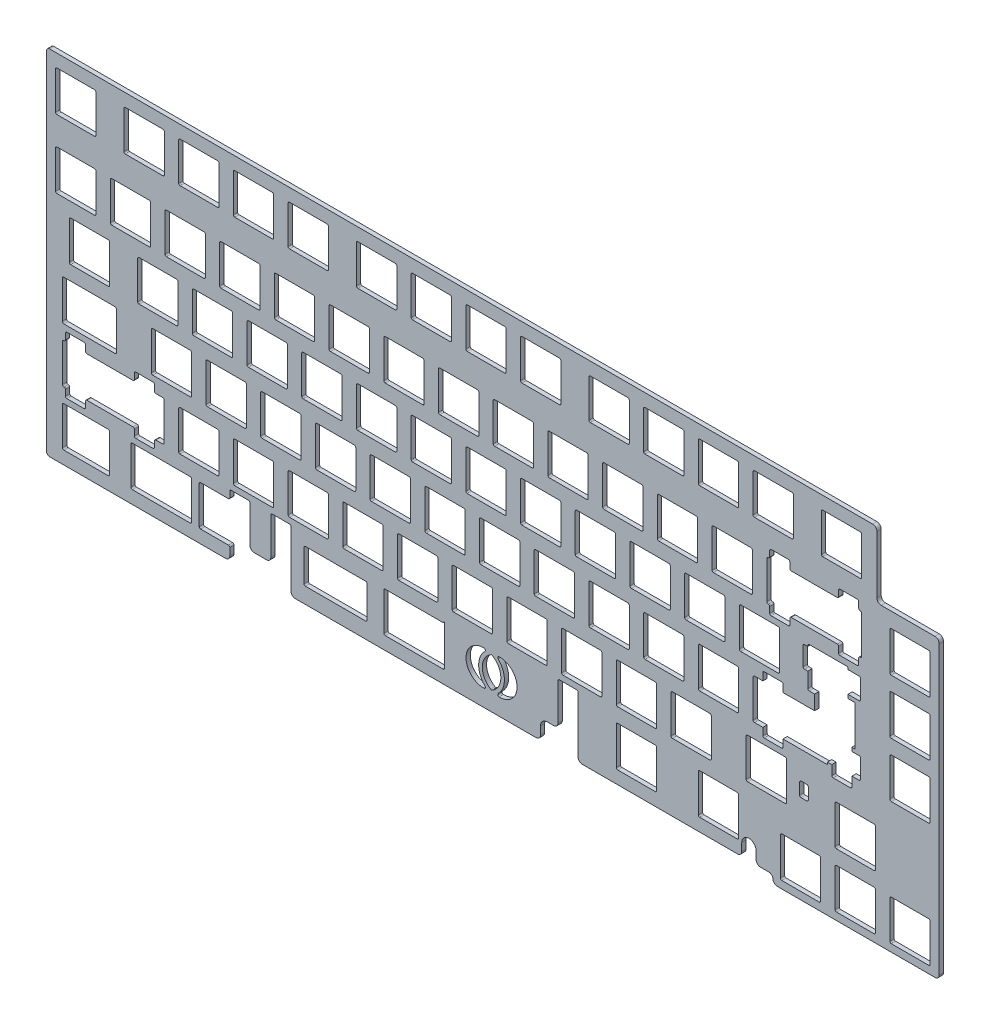
SolidWorks part; units mm, degrees
material "POM Acetal Copolymer"
ref_plane "Front Plane" through (0, 0, 0) normal (0, 0, 1) x (1, 0, 0)
ref_plane "Top Plane" through (0, 0, 0) normal (0, 1, 0) x (1, 0, 0)
ref_plane "Right Plane" through (0, 0, 0) normal (1, 0, 0) x (0, 0, -1)
sketch "Model" plane through (0, 0, 0) normal (0, 0, 1) x (1, 0, 0)
  line L0 (274.4928, 83.607) -> (287.4928, 83.607)
  line L1 (273.9928, 70.107) -> (273.9928, 75.3421)
  line L2 (8.8553, 129.8695) -> (8.8553, 63.082)
  line L3 (67.4518, 130.9695) -> (9.9553, 130.9695)
  line L4 (319.7678, 63.082) -> (319.7678, 106.4532)
  line L5 (195.4959, 7.957) -> (249.4928, 7.957)
  line L6 (86.9959, 28.958) -> (86.9959, 16.157)
  line L7 (187.4959, 29.458) -> (193.4959, 29.458)
  line L8 (193.9959, 28.958) -> (193.9959, 9.457)
  line L9 (186.9959, 16.157) -> (186.9959, 28.958)
  line L10 (87.4959, 29.458) -> (93.4959, 29.458)
  line L11 (126.357, 12.957) -> (126.357, 25.957)
  line L12 (62.0594, 12.957) -> (62.0594, 25.957)
  line L13 (38.2454, 12.957) -> (38.2454, 25.957)
  line L14 (14.4343, 12.957) -> (14.4343, 25.957)
  line L15 (72.207, 12.457) -> (62.5594, 12.457)
  line L16 (62.5594, 26.457) -> (72.207, 26.457)
  line L17 (59.3945, 25.957) -> (59.3945, 12.957)
  line L18 (58.8945, 12.457) -> (38.7454, 12.457)
  line L19 (38.7454, 26.457) -> (58.8945, 26.457)
  line L20 (30.8195, 25.957) -> (30.8195, 12.957)
  line L21 (30.3195, 12.457) -> (14.9343, 12.457)
  line L22 (14.9343, 26.457) -> (30.3195, 26.457)
  line L23 (93.9959, 28.958) -> (93.9959, 9.457)
  line L24 (146.9959, 12.457) -> (126.857, 12.457)
  line L25 (126.857, 26.457) -> (146.9959, 26.457)
  line L26 (147.4959, 26.7823) -> (147.4959, 12.957)
  line L27 (9.9553, 7.957) -> (71.207, 7.957)
  line L28 (95.4959, 7.957) -> (179.3625, 7.957)
  line L29 (263.3678, 5.0945) -> (318.2678, 5.0945)
  line L30 (180.8625, 12.157) -> (180.8625, 9.457)
  line L31 (250.9928, 12.157) -> (250.9928, 9.457)
  line L32 (255.9928, 12.157) -> (255.9928, 9.457)
  line L33 (183.3625, 14.657) -> (185.4959, 14.657)
  line L34 (81.207, 14.657) -> (85.4959, 14.657)
  line L35 (257.4928, 7.957) -> (260.371, 7.957)
  line L36 (8.8553, 63.082) -> (8.8553, 9.057)
  line L37 (319.7678, 63.082) -> (319.7678, 6.5945)
  line L38 (75.4518, 130.9695) -> (248.4268, 130.9695)
  line L39 (256.4268, 130.9695) -> (296.5553, 130.9695)
  line L40 (298.0553, 129.4695) -> (298.0553, 109.4532)
  line L41 (299.5553, 107.9532) -> (318.2678, 107.9532)
  line L42 (271.6572, 41.007) -> (273.6572, 41.007)
  line L43 (274.1572, 40.507) -> (274.1572, 36.507)
  line L44 (273.6572, 36.007) -> (271.6572, 36.007)
  line L45 (271.1572, 36.507) -> (271.1572, 40.507)
  line L46 (260.7295, 105.157) -> (260.7295, 103.157)
  line L47 (268.2295, 102.657) -> (284.2295, 102.657)
  line L48 (268.2295, 88.657) -> (284.2295, 88.657)
  line L49 (261.2295, 105.657) -> (267.2295, 105.657)
  line L50 (261.2295, 85.657) -> (267.2295, 85.657)
  line L51 (267.7295, 103.157) -> (267.7295, 105.157)
  line L52 (267.7295, 88.157) -> (267.7295, 86.157)
  line L53 (291.7295, 105.157) -> (291.7295, 103.157)
  line L54 (291.2295, 105.657) -> (285.2295, 105.657)
  line L55 (291.2295, 85.657) -> (285.2295, 85.657)
  line L56 (284.7295, 103.157) -> (284.7295, 105.157)
  line L57 (284.7295, 88.157) -> (284.7295, 86.157)
  line L58 (258.3508, 50.557) -> (258.3508, 48.057)
  line L59 (265.3508, 50.557) -> (280.8516, 50.557)
  line L60 (258.8508, 67.557) -> (264.8508, 67.557)
  line L61 (258.8508, 47.557) -> (264.8508, 47.557)
  line L62 (265.3508, 64.557) -> (265.3508, 67.057)
  line L63 (265.3508, 50.557) -> (265.3508, 48.057)
  line L64 (288.8508, 47.557) -> (282.8508, 47.557)
  line L65 (282.3508, 51.3421) -> (282.3508, 48.057)
  line L66 (15.4632, 48.0073) -> (15.4632, 46.007)
  line L67 (22.9632, 45.5073) -> (38.9632, 45.5073)
  line L68 (22.9632, 31.5073) -> (38.9632, 31.5073)
  line L69 (15.9632, 48.5073) -> (21.9632, 48.5073)
  line L70 (15.9632, 28.5073) -> (21.9632, 28.5073)
  line L71 (22.4632, 46.0073) -> (22.4632, 48.0073)
  line L72 (22.4632, 31.0073) -> (22.4632, 29.0073)
  line L73 (46.4632, 48.0073) -> (46.4632, 46.007)
  line L74 (45.9632, 48.5073) -> (39.9632, 48.5073)
  line L75 (45.9632, 28.5073) -> (39.9632, 28.5073)
  line L76 (39.4632, 46.0073) -> (39.4632, 48.0073)
  line L77 (39.4632, 31.0073) -> (39.4632, 29.0073)
  line L78 (258.3508, 50.557) -> (255.4453, 50.557)
  line L79 (276.3765, 69.607) -> (274.4928, 69.607)
  line L80 (276.3765, 64.557) -> (276.3765, 69.607)
  line L81 (292.3508, 82.2801) -> (292.3508, 75.8421)
  line L82 (292.3508, 58.2801) -> (292.3508, 51.8421)
  line L83 (291.8508, 82.7801) -> (287.9953, 82.7801)
  line L84 (255.4453, 64.557) -> (258.3508, 64.557)
  line L85 (290.3765, 74.0611) -> (290.3765, 60.0611)
  line L86 (254.9453, 64.057) -> (254.9453, 51.057)
  line L87 (287.9953, 75.3421) -> (291.8508, 75.3421)
  line L88 (289.3508, 58.7801) -> (291.8508, 58.7801)
  line L89 (290.3765, 74.0611) -> (287.9953, 74.0611)
  line L90 (287.9953, 74.0611) -> (287.9953, 75.3421)
  line L91 (289.3508, 58.7801) -> (289.3508, 60.0611)
  line L92 (289.3508, 60.0611) -> (290.3765, 60.0611)
  line L93 (282.3508, 51.3421) -> (280.8516, 51.3421)
  line L94 (280.8516, 51.3421) -> (280.8516, 50.557)
  line L95 (258.3508, 67.057) -> (258.3508, 64.557)
  line L96 (289.3508, 48.057) -> (289.3508, 51.3421)
  line L97 (291.8508, 51.3421) -> (289.3508, 51.3421)
  line L98 (287.9928, 83.107) -> (287.9953, 82.7801)
  line L99 (265.3508, 64.557) -> (276.3765, 64.557)
  line L100 (272.3508, 82.2801) -> (272.3508, 75.8421)
  line L101 (272.8508, 82.7801) -> (273.9928, 82.7801)
  line L102 (273.9928, 75.3421) -> (272.8508, 75.3421)
  line L103 (273.9928, 82.7801) -> (273.9928, 83.107)
  line L104 (259.7053, 89.157) -> (259.7053, 102.157)
  line L105 (292.7553, 102.157) -> (292.7553, 89.157)
  line L106 (291.7295, 86.157) -> (291.7295, 88.157)
  line L107 (292.2295, 88.657) -> (292.2553, 88.657)
  line L108 (292.2295, 102.657) -> (292.2553, 102.657)
  line L109 (260.2053, 102.657) -> (260.2295, 102.657)
  line L110 (260.7295, 86.157) -> (260.7295, 88.157)
  line L111 (260.2295, 88.657) -> (260.2053, 88.657)
  line L112 (49.8678, 45.007) -> (49.8678, 32.007)
  line L113 (46.4632, 29.0073) -> (46.4632, 31.007)
  line L114 (46.9632, 31.507) -> (49.3678, 31.507)
  line L115 (46.9632, 45.507) -> (49.3678, 45.507)
  line L116 (14.4365, 32.007) -> (14.4365, 45.007)
  line L117 (15.4632, 29.0073) -> (15.4632, 31.007)
  line L118 (14.9632, 31.507) -> (14.9365, 31.507)
  line L119 (14.9365, 45.507) -> (14.9632, 45.507)
  line L120 (79.707, 28.958) -> (79.707, 16.157)
  line L121 (72.707, 11.957) -> (72.707, 9.457)
  line L122 (72.707, 26.957) -> (72.707, 28.958)
  line L123 (73.207, 29.458) -> (79.207, 29.458)
  line L124 (120.5413, 13.957) -> (120.5413, 24.957)
  line L125 (99.0413, 13.457) -> (120.0413, 13.457)
  line L126 (98.5413, 24.957) -> (98.5413, 13.957)
  line L127 (120.0413, 25.457) -> (99.0413, 25.457)
  line L144 (12.5303, 112.4445) -> (25.5803, 112.4445)
  line L145 (26.0803, 112.9445) -> (26.0803, 125.9945)
  line L146 (25.5803, 126.4945) -> (12.5303, 126.4945)
  line L147 (12.0303, 125.9945) -> (12.0303, 112.9445)
  line L148 (36.3428, 112.4445) -> (49.3928, 112.4445)
  line L149 (49.8928, 112.9445) -> (49.8928, 125.9945)
  line L150 (49.3928, 126.4945) -> (36.3428, 126.4945)
  line L151 (35.8428, 125.9945) -> (35.8428, 112.9445)
  line L152 (93.4928, 112.4445) -> (106.5428, 112.4445)
  line L153 (107.0428, 112.9445) -> (107.0428, 125.9945)
  line L154 (106.5428, 126.4945) -> (93.4928, 126.4945)
  line L155 (92.9928, 125.9945) -> (92.9928, 112.9445)
  line L156 (117.3053, 112.4445) -> (130.3553, 112.4445)
  line L157 (130.8553, 112.9445) -> (130.8553, 125.9945)
  line L158 (130.3553, 126.4945) -> (117.3053, 126.4945)
  line L159 (116.8053, 125.9945) -> (116.8053, 112.9445)
  line L160 (136.3553, 112.4445) -> (149.4053, 112.4445)
  line L161 (149.9053, 112.9445) -> (149.9053, 125.9945)
  line L162 (149.4053, 126.4945) -> (136.3553, 126.4945)
  line L163 (135.8553, 125.9945) -> (135.8553, 112.9445)
  line L164 (155.4053, 112.4445) -> (168.4553, 112.4445)
  line L165 (168.9553, 112.9445) -> (168.9553, 125.9945)
  line L166 (168.4553, 126.4945) -> (155.4053, 126.4945)
  line L167 (154.9053, 125.9945) -> (154.9053, 112.9445)
  line L168 (174.4553, 112.4445) -> (187.5053, 112.4445)
  line L169 (188.0053, 112.9445) -> (188.0053, 125.9945)
  line L170 (187.5053, 126.4945) -> (174.4553, 126.4945)
  line L171 (173.9553, 125.9945) -> (173.9553, 112.9445)
  line L172 (198.2678, 112.4445) -> (211.3178, 112.4445)
  line L173 (211.8178, 112.9445) -> (211.8178, 125.9945)
  line L174 (211.3178, 126.4945) -> (198.2678, 126.4945)
  line L175 (197.7678, 125.9945) -> (197.7678, 112.9445)
  line L176 (217.3178, 112.4445) -> (230.3678, 112.4445)
  line L177 (230.8678, 112.9445) -> (230.8678, 125.9945)
  line L178 (230.3678, 126.4945) -> (217.3178, 126.4945)
  line L179 (216.8178, 125.9945) -> (216.8178, 112.9445)
  line L180 (279.2303, 112.4445) -> (292.2803, 112.4445)
  line L181 (292.7803, 112.9445) -> (292.7803, 125.9945)
  line L182 (292.2803, 126.4945) -> (279.2303, 126.4945)
  line L183 (278.7303, 125.9945) -> (278.7303, 112.9445)
  line L184 (303.0428, 88.632) -> (316.0928, 88.632)
  line L185 (316.5928, 89.132) -> (316.5928, 102.182)
  line L186 (316.0928, 102.682) -> (303.0428, 102.682)
  line L187 (302.5428, 102.182) -> (302.5428, 89.132)
  line L188 (283.9928, 26.7195) -> (297.0428, 26.7195)
  line L189 (297.5428, 27.2195) -> (297.5428, 40.2695)
  line L190 (297.0428, 40.7695) -> (283.9928, 40.7695)
  line L191 (283.4928, 40.2695) -> (283.4928, 27.2195)
  line L192 (303.0428, 7.6695) -> (316.0928, 7.6695)
  line L193 (316.5928, 8.1695) -> (316.5928, 21.2195)
  line L194 (316.0928, 21.7195) -> (303.0428, 21.7195)
  line L195 (302.5428, 21.2195) -> (302.5428, 8.1695)
  line L196 (283.9928, 7.6695) -> (297.0428, 7.6695)
  line L197 (297.5428, 8.1695) -> (297.5428, 21.2195)
  line L198 (297.0428, 21.7195) -> (283.9928, 21.7195)
  line L199 (283.4928, 21.2195) -> (283.4928, 8.1695)
  line L200 (264.9428, 7.6695) -> (277.9928, 7.6695)
  line L201 (278.4928, 8.1695) -> (278.4928, 21.2195)
  line L202 (277.9928, 21.7195) -> (264.9428, 21.7195)
  line L203 (264.4428, 21.2195) -> (264.4428, 8.1695)
  line L204 (236.3678, 12.432) -> (249.4178, 12.432)
  line L205 (249.9178, 12.932) -> (249.9178, 25.982)
  line L206 (249.4178, 26.482) -> (236.3678, 26.482)
  line L207 (235.8678, 25.982) -> (235.8678, 12.932)
  line L208 (207.7928, 12.432) -> (220.8428, 12.432)
  line L209 (221.3428, 12.932) -> (221.3428, 25.982)
  line L210 (220.8428, 26.482) -> (207.7928, 26.482)
  line L211 (207.2928, 25.982) -> (207.2928, 12.932)
  line L212 (253.0365, 31.482) -> (266.0865, 31.482)
  line L213 (266.5865, 31.982) -> (266.5865, 45.032)
  line L214 (266.0865, 45.532) -> (253.0365, 45.532)
  line L215 (252.5365, 45.032) -> (252.5365, 31.982)
  line L216 (226.8428, 31.482) -> (239.8928, 31.482)
  line L217 (240.3928, 31.982) -> (240.3928, 45.032)
  line L218 (239.8928, 45.532) -> (226.8428, 45.532)
  line L219 (226.3428, 45.032) -> (226.3428, 31.982)
  line L220 (207.7928, 31.482) -> (220.8428, 31.482)
  line L221 (221.3428, 31.982) -> (221.3428, 45.032)
  line L222 (220.8428, 45.532) -> (207.7928, 45.532)
  line L223 (207.2928, 45.032) -> (207.2928, 31.982)
  line L224 (188.7428, 31.482) -> (201.7928, 31.482)
  line L225 (202.2928, 31.982) -> (202.2928, 45.032)
  line L226 (201.7928, 45.532) -> (188.7428, 45.532)
  line L227 (188.2428, 45.032) -> (188.2428, 31.982)
  line L228 (169.6928, 31.482) -> (182.7428, 31.482)
  line L229 (183.2428, 31.982) -> (183.2428, 45.032)
  line L230 (182.7428, 45.532) -> (169.6928, 45.532)
  line L231 (169.1928, 45.032) -> (169.1928, 31.982)
  line L232 (150.6428, 31.482) -> (163.6928, 31.482)
  line L233 (164.1928, 31.982) -> (164.1928, 45.032)
  line L234 (163.6928, 45.532) -> (150.6428, 45.532)
  line L235 (150.1428, 45.032) -> (150.1428, 31.982)
  line L236 (131.5928, 31.482) -> (144.6428, 31.482)
  line L237 (145.1428, 31.982) -> (145.1428, 45.032)
  line L238 (144.6428, 45.532) -> (131.5928, 45.532)
  line L239 (131.0928, 45.032) -> (131.0928, 31.982)
  line L240 (112.5428, 31.482) -> (125.5928, 31.482)
  line L241 (126.0928, 31.982) -> (126.0928, 45.032)
  line L242 (125.5928, 45.532) -> (112.5428, 45.532)
  line L243 (112.0428, 45.032) -> (112.0428, 31.982)
  line L244 (93.4928, 31.482) -> (106.5428, 31.482)
  line L245 (107.0428, 31.982) -> (107.0428, 45.032)
  line L246 (106.5428, 45.532) -> (93.4928, 45.532)
  line L247 (92.9928, 45.032) -> (92.9928, 31.982)
  line L248 (74.4428, 31.482) -> (87.4928, 31.482)
  line L249 (87.9928, 31.982) -> (87.9928, 45.032)
  line L250 (87.4928, 45.532) -> (74.4428, 45.532)
  line L251 (73.9428, 45.032) -> (73.9428, 31.982)
  line L252 (55.3928, 31.482) -> (68.4428, 31.482)
  line L253 (68.9428, 31.982) -> (68.9428, 45.032)
  line L254 (68.4428, 45.532) -> (55.3928, 45.532)
  line L255 (54.8928, 45.032) -> (54.8928, 31.982)
  line L256 (45.8678, 50.532) -> (58.9178, 50.532)
  line L257 (59.4178, 51.032) -> (59.4178, 64.082)
  line L258 (58.9178, 64.582) -> (45.8678, 64.582)
  line L259 (45.3678, 64.082) -> (45.3678, 51.032)
  line L260 (64.9178, 50.532) -> (77.9678, 50.532)
  line L261 (78.4678, 51.032) -> (78.4678, 64.082)
  line L262 (77.9678, 64.582) -> (64.9178, 64.582)
  line L263 (64.4178, 64.082) -> (64.4178, 51.032)
  line L264 (83.9678, 50.532) -> (97.0178, 50.532)
  line L265 (97.5178, 51.032) -> (97.5178, 64.082)
  line L266 (97.0178, 64.582) -> (83.9678, 64.582)
  line L267 (83.4678, 64.082) -> (83.4678, 51.032)
  line L268 (103.0178, 50.532) -> (116.0678, 50.532)
  line L269 (116.5678, 51.032) -> (116.5678, 64.082)
  line L270 (116.0678, 64.582) -> (103.0178, 64.582)
  line L271 (102.5178, 64.082) -> (102.5178, 51.032)
  line L272 (122.0678, 50.532) -> (135.1178, 50.532)
  line L273 (135.6178, 51.032) -> (135.6178, 64.082)
  line L274 (135.1178, 64.582) -> (122.0678, 64.582)
  line L275 (121.5678, 64.082) -> (121.5678, 51.032)
  line L276 (141.1178, 50.532) -> (154.1678, 50.532)
  line L277 (154.6678, 51.032) -> (154.6678, 64.082)
  line L278 (154.1678, 64.582) -> (141.1178, 64.582)
  line L279 (140.6178, 64.082) -> (140.6178, 51.032)
  line L280 (160.1678, 50.532) -> (173.2178, 50.532)
  line L281 (173.7178, 51.032) -> (173.7178, 64.082)
  line L282 (173.2178, 64.582) -> (160.1678, 64.582)
  line L283 (159.6678, 64.082) -> (159.6678, 51.032)
  line L284 (179.2178, 50.532) -> (192.2678, 50.532)
  line L285 (192.7678, 51.032) -> (192.7678, 64.082)
  line L286 (192.2678, 64.582) -> (179.2178, 64.582)
  line L287 (178.7178, 64.082) -> (178.7178, 51.032)
  line L288 (198.2678, 50.532) -> (211.3178, 50.532)
  line L289 (211.8178, 51.032) -> (211.8178, 64.082)
  line L290 (211.3178, 64.582) -> (198.2678, 64.582)
  line L291 (197.7678, 64.082) -> (197.7678, 51.032)
  line L292 (217.3178, 50.532) -> (230.3678, 50.532)
  line L293 (230.8678, 51.032) -> (230.8678, 64.082)
  line L294 (230.3678, 64.582) -> (217.3178, 64.582)
  line L295 (216.8178, 64.082) -> (216.8178, 51.032)
  line L296 (236.3678, 50.532) -> (249.4178, 50.532)
  line L297 (249.9178, 51.032) -> (249.9178, 64.082)
  line L298 (249.4178, 64.582) -> (236.3678, 64.582)
  line L299 (235.8678, 64.082) -> (235.8678, 51.032)
  line L300 (17.2928, 69.582) -> (30.3428, 69.582)
  line L301 (30.8428, 70.082) -> (30.8428, 83.132)
  line L302 (30.3428, 83.632) -> (17.2928, 83.632)
  line L303 (16.7928, 83.132) -> (16.7928, 70.082)
  line L304 (12.5303, 88.632) -> (25.5803, 88.632)
  line L305 (26.0803, 89.132) -> (26.0803, 102.182)
  line L306 (25.5803, 102.682) -> (12.5303, 102.682)
  line L307 (12.0303, 102.182) -> (12.0303, 89.132)
  line L308 (31.5803, 88.632) -> (44.6303, 88.632)
  line L309 (45.1303, 89.132) -> (45.1303, 102.182)
  line L310 (44.6303, 102.682) -> (31.5803, 102.682)
  line L311 (31.0803, 102.182) -> (31.0803, 89.132)
  line L312 (50.6303, 88.632) -> (63.6803, 88.632)
  line L313 (64.1803, 89.132) -> (64.1803, 102.182)
  line L314 (63.6803, 102.682) -> (50.6303, 102.682)
  line L315 (50.1303, 102.182) -> (50.1303, 89.132)
  line L316 (69.6803, 88.632) -> (82.7303, 88.632)
  line L317 (83.2303, 89.132) -> (83.2303, 102.182)
  line L318 (82.7303, 102.682) -> (69.6803, 102.682)
  line L319 (69.1803, 102.182) -> (69.1803, 89.132)
  line L320 (88.7303, 88.632) -> (101.7803, 88.632)
  line L321 (102.2803, 89.132) -> (102.2803, 102.182)
  line L322 (101.7803, 102.682) -> (88.7303, 102.682)
  line L323 (88.2303, 102.182) -> (88.2303, 89.132)
  line L324 (107.7803, 88.632) -> (120.8303, 88.632)
  line L325 (121.3303, 89.132) -> (121.3303, 102.182)
  line L326 (120.8303, 102.682) -> (107.7803, 102.682)
  line L327 (107.2803, 102.182) -> (107.2803, 89.132)
  line L328 (126.8303, 88.632) -> (139.8803, 88.632)
  line L329 (140.3803, 89.132) -> (140.3803, 102.182)
  line L330 (139.8803, 102.682) -> (126.8303, 102.682)
  line L331 (126.3303, 102.182) -> (126.3303, 89.132)
  line L332 (145.8803, 88.632) -> (158.9303, 88.632)
  line L333 (159.4303, 89.132) -> (159.4303, 102.182)
  line L334 (158.9303, 102.682) -> (145.8803, 102.682)
  line L335 (145.3803, 102.182) -> (145.3803, 89.132)
  line L336 (164.9303, 88.632) -> (177.9803, 88.632)
  line L337 (178.4803, 89.132) -> (178.4803, 102.182)
  line L338 (177.9803, 102.682) -> (164.9303, 102.682)
  line L339 (164.4303, 102.182) -> (164.4303, 89.132)
  line L340 (183.9803, 88.632) -> (197.0303, 88.632)
  line L341 (197.5303, 89.132) -> (197.5303, 102.182)
  line L342 (197.0303, 102.682) -> (183.9803, 102.682)
  line L343 (183.4803, 102.182) -> (183.4803, 89.132)
  line L344 (203.0303, 88.632) -> (216.0803, 88.632)
  line L345 (216.5803, 89.132) -> (216.5803, 102.182)
  line L346 (216.0803, 102.682) -> (203.0303, 102.682)
  line L347 (202.5303, 102.182) -> (202.5303, 89.132)
  line L348 (222.0803, 88.632) -> (235.1303, 88.632)
  line L349 (235.6303, 89.132) -> (235.6303, 102.182)
  line L350 (235.1303, 102.682) -> (222.0803, 102.682)
  line L351 (221.5803, 102.182) -> (221.5803, 89.132)
  line L352 (241.1303, 88.632) -> (254.1803, 88.632)
  line L353 (254.6803, 89.132) -> (254.6803, 102.182)
  line L354 (254.1803, 102.682) -> (241.1303, 102.682)
  line L355 (240.6303, 102.182) -> (240.6303, 89.132)
  line L356 (41.1053, 69.582) -> (54.1553, 69.582)
  line L357 (54.6553, 70.082) -> (54.6553, 83.132)
  line L358 (54.1553, 83.632) -> (41.1053, 83.632)
  line L359 (40.6053, 83.132) -> (40.6053, 70.082)
  line L360 (60.1553, 69.582) -> (73.2053, 69.582)
  line L361 (73.7053, 70.082) -> (73.7053, 83.132)
  line L362 (73.2053, 83.632) -> (60.1553, 83.632)
  line L363 (59.6553, 83.132) -> (59.6553, 70.082)
  line L364 (79.2053, 69.582) -> (92.2553, 69.582)
  line L365 (92.7553, 70.082) -> (92.7553, 83.132)
  line L366 (92.2553, 83.632) -> (79.2053, 83.632)
  line L367 (78.7053, 83.132) -> (78.7053, 70.082)
  line L368 (98.2553, 69.582) -> (111.3053, 69.582)
  line L369 (111.8053, 70.082) -> (111.8053, 83.132)
  line L370 (111.3053, 83.632) -> (98.2553, 83.632)
  line L371 (97.7553, 83.132) -> (97.7553, 70.082)
  line L372 (117.3053, 69.582) -> (130.3553, 69.582)
  line L373 (130.8553, 70.082) -> (130.8553, 83.132)
  line L374 (130.3553, 83.632) -> (117.3053, 83.632)
  line L375 (116.8053, 83.132) -> (116.8053, 70.082)
  line L376 (136.3553, 69.582) -> (149.4053, 69.582)
  line L377 (149.9053, 70.082) -> (149.9053, 83.132)
  line L378 (149.4053, 83.632) -> (136.3553, 83.632)
  line L379 (135.8553, 83.132) -> (135.8553, 70.082)
  line L380 (155.4053, 69.582) -> (168.4553, 69.582)
  line L381 (168.9553, 70.082) -> (168.9553, 83.132)
  line L382 (168.4553, 83.632) -> (155.4053, 83.632)
  line L383 (154.9053, 83.132) -> (154.9053, 70.082)
  line L384 (174.4553, 69.582) -> (187.5053, 69.582)
  line L385 (188.0053, 70.082) -> (188.0053, 83.132)
  line L386 (187.5053, 83.632) -> (174.4553, 83.632)
  line L387 (173.9553, 83.132) -> (173.9553, 70.082)
  line L388 (193.5053, 69.582) -> (206.5553, 69.582)
  line L389 (207.0553, 70.082) -> (207.0553, 83.132)
  line L390 (206.5553, 83.632) -> (193.5053, 83.632)
  line L391 (193.0053, 83.132) -> (193.0053, 70.082)
  line L392 (212.5553, 69.582) -> (225.6053, 69.582)
  line L393 (226.1053, 70.082) -> (226.1053, 83.132)
  line L394 (225.6053, 83.632) -> (212.5553, 83.632)
  line L395 (212.0553, 83.132) -> (212.0553, 70.082)
  line L396 (231.6053, 69.582) -> (244.6553, 69.582)
  line L397 (245.1553, 70.082) -> (245.1553, 83.132)
  line L398 (244.6553, 83.632) -> (231.6053, 83.632)
  line L399 (231.1053, 83.132) -> (231.1053, 70.082)
  line L400 (250.6553, 69.582) -> (263.7053, 69.582)
  line L401 (264.2053, 70.082) -> (264.2053, 83.132)
  line L402 (263.7053, 83.632) -> (250.6553, 83.632)
  line L403 (250.1553, 83.132) -> (250.1553, 70.082)
  line L404 (303.0428, 69.582) -> (316.0928, 69.582)
  line L405 (316.5928, 70.082) -> (316.5928, 83.132)
  line L406 (316.0928, 83.632) -> (303.0428, 83.632)
  line L407 (302.5428, 83.132) -> (302.5428, 70.082)
  line L408 (303.0678, 64.582) -> (316.1178, 64.582)
  line L409 (302.5428, 51.057) -> (302.5428, 64.057)
  line L410 (316.0678, 50.532) -> (303.0678, 50.532)
  line L411 (316.5928, 64.107) -> (316.5928, 51.057)
  line L412 (32.699, 50.507) -> (14.9365, 50.507)
  line L413 (33.249, 64.057) -> (33.249, 51.057)
  line L414 (14.9365, 64.607) -> (32.699, 64.607)
  line L415 (14.3865, 51.057) -> (14.3865, 64.057)
  line L416 (236.3678, 112.4445) -> (249.4178, 112.4445)
  line L417 (249.9178, 112.9445) -> (249.9178, 125.9945)
  line L418 (249.4178, 126.4945) -> (236.3678, 126.4945)
  line L419 (235.8678, 125.9945) -> (235.8678, 112.9445)
  line L420 (255.4178, 112.4445) -> (268.4678, 112.4445)
  line L421 (268.9678, 112.9445) -> (268.9678, 125.9945)
  line L422 (268.4678, 126.4945) -> (255.4178, 126.4945)
  line L423 (254.9178, 125.9945) -> (254.9178, 112.9445)
  line L424 (55.3928, 112.4445) -> (68.4428, 112.4445)
  line L425 (68.9428, 112.9445) -> (68.9428, 125.9945)
  line L426 (68.4428, 126.4945) -> (55.3928, 126.4945)
  line L427 (54.8928, 125.9945) -> (54.8928, 112.9445)
  line L428 (74.4428, 112.4445) -> (87.4928, 112.4445)
  line L429 (87.9928, 112.9445) -> (87.9928, 125.9945)
  line L430 (87.4928, 126.4945) -> (74.4428, 126.4945)
  line L431 (73.9428, 125.9945) -> (73.9428, 112.9445)
  line L432 (67.4518, 130.9695) -> (75.4518, 130.9695)
  line L433 (248.4268, 130.9695) -> (256.4268, 130.9695)
  arc A0 (319.7678, 106.4532) -> (318.2678, 107.9532) centre (318.2678, 106.4532) ccw
  arc A1 (318.2678, 5.0945) -> (319.7678, 6.5945) centre (318.2678, 6.5945) ccw
  arc A2 (193.9959, 9.457) -> (195.4959, 7.957) centre (195.4959, 9.457) ccw
  arc A3 (273.9928, 70.107) -> (274.4928, 69.607) centre (274.4928, 70.107) ccw
  arc A4 (287.9928, 83.107) -> (287.4928, 83.607) centre (287.4928, 83.107) ccw
  arc A5 (274.4928, 83.607) -> (273.9928, 83.107) centre (274.4928, 83.107) ccw
  arc A6 (8.8553, 9.057) -> (9.9553, 7.957) centre (9.9553, 9.057) ccw
  arc A7 (9.9553, 130.9695) -> (8.8553, 129.8695) centre (9.9553, 129.8695) ccw
  arc A8 (85.4959, 14.657) -> (86.9959, 16.157) centre (85.4959, 16.157) ccw
  arc A9 (193.9959, 28.958) -> (193.4959, 29.458) centre (193.4959, 28.958) ccw
  arc A10 (187.4959, 29.458) -> (186.9959, 28.958) centre (187.4959, 28.958) ccw
  arc A11 (185.4959, 14.657) -> (186.9959, 16.157) centre (185.4959, 16.157) ccw
  arc A12 (87.4959, 29.458) -> (86.9959, 28.958) centre (87.4959, 28.958) ccw
  arc A13 (126.357, 12.957) -> (126.857, 12.457) centre (126.857, 12.957) ccw
  arc A14 (93.9959, 28.958) -> (93.4959, 29.458) centre (93.4959, 28.958) ccw
  arc A15 (38.7454, 26.457) -> (38.2454, 25.957) centre (38.7454, 25.957) ccw
  arc A16 (14.9343, 26.457) -> (14.4343, 25.957) centre (14.9343, 25.957) ccw
  arc A17 (62.0594, 12.957) -> (62.5594, 12.457) centre (62.5594, 12.957) ccw
  arc A18 (62.5594, 26.457) -> (62.0594, 25.957) centre (62.5594, 25.957) ccw
  arc A19 (38.2454, 12.957) -> (38.7454, 12.457) centre (38.7454, 12.957) ccw
  arc A20 (58.8945, 12.457) -> (59.3945, 12.957) centre (58.8945, 12.957) ccw
  arc A21 (59.3945, 25.957) -> (58.8945, 26.457) centre (58.8945, 25.957) ccw
  arc A22 (30.3195, 12.457) -> (30.8195, 12.957) centre (30.3195, 12.957) ccw
  arc A23 (14.4343, 12.957) -> (14.9343, 12.457) centre (14.9343, 12.957) ccw
  arc A24 (30.8195, 25.957) -> (30.3195, 26.457) centre (30.3195, 25.957) ccw
  arc A25 (126.857, 26.457) -> (126.357, 25.957) centre (126.857, 25.957) ccw
  arc A26 (146.9959, 12.457) -> (147.4959, 12.957) centre (146.9959, 12.957) ccw
  arc A27 (147.4959, 26.7823) -> (146.9959, 26.457) centre (147.4647, 26.2833) ccw
  arc A28 (93.9959, 9.457) -> (95.4959, 7.957) centre (95.4959, 9.457) ccw
  arc A29 (261.8694, 6.5258) -> (263.3678, 5.0945) centre (263.3678, 6.5945) ccw
  arc A30 (261.8694, 6.5258) -> (260.371, 7.957) centre (260.371, 6.457) ccw
  arc A31 (179.3625, 7.957) -> (180.8625, 9.457) centre (179.3625, 9.457) ccw
  arc A32 (255.9928, 9.457) -> (257.4928, 7.957) centre (257.4928, 9.457) ccw
  arc A33 (249.4928, 7.957) -> (250.9928, 9.457) centre (249.4928, 9.457) ccw
  arc A34 (255.9928, 12.157) -> (250.9928, 12.157) centre (253.4928, 12.157) ccw
  arc A35 (183.3625, 14.657) -> (180.8625, 12.157) centre (183.3625, 12.157) ccw
  arc A36 (298.0553, 129.4695) -> (296.5553, 130.9695) centre (296.5553, 129.4695) ccw
  arc A37 (298.0553, 109.4532) -> (299.5553, 107.9532) centre (299.5553, 109.4532) ccw
  arc A38 (271.6572, 41.007) -> (271.1572, 40.507) centre (271.6572, 40.507) ccw
  arc A39 (274.1572, 40.507) -> (273.6572, 41.007) centre (273.6572, 40.507) ccw
  arc A40 (273.6572, 36.007) -> (274.1572, 36.507) centre (273.6572, 36.507) ccw
  arc A41 (271.1572, 36.507) -> (271.6572, 36.007) centre (271.6572, 36.507) ccw
  arc A42 (260.2295, 102.657) -> (260.7295, 103.157) centre (260.2295, 103.157) ccw
  arc A43 (267.7295, 103.157) -> (268.2295, 102.657) centre (268.2295, 103.157) ccw
  arc A44 (261.2295, 105.657) -> (260.7295, 105.157) centre (261.2295, 105.157) ccw
  arc A45 (260.7295, 86.157) -> (261.2295, 85.657) centre (261.2295, 86.157) ccw
  arc A46 (267.7295, 105.157) -> (267.2295, 105.657) centre (267.2295, 105.157) ccw
  arc A47 (268.2295, 88.657) -> (267.7295, 88.157) centre (268.2295, 88.157) ccw
  arc A48 (267.2295, 85.657) -> (267.7295, 86.157) centre (267.2295, 86.157) ccw
  arc A49 (284.2295, 102.657) -> (284.7295, 103.157) centre (284.2295, 103.157) ccw
  arc A50 (291.7295, 105.157) -> (291.2295, 105.657) centre (291.2295, 105.157) ccw
  arc A51 (291.2295, 85.657) -> (291.7295, 86.157) centre (291.2295, 86.157) ccw
  arc A52 (285.2295, 105.657) -> (284.7295, 105.157) centre (285.2295, 105.157) ccw
  arc A53 (284.7295, 88.157) -> (284.2295, 88.657) centre (284.2295, 88.157) ccw
  arc A54 (284.7295, 86.157) -> (285.2295, 85.657) centre (285.2295, 86.157) ccw
  arc A55 (258.8508, 67.557) -> (258.3508, 67.057) centre (258.8508, 67.057) ccw
  arc A56 (258.3508, 48.057) -> (258.8508, 47.557) centre (258.8508, 48.057) ccw
  arc A57 (265.3508, 67.057) -> (264.8508, 67.557) centre (264.8508, 67.057) ccw
  arc A58 (264.8508, 47.557) -> (265.3508, 48.057) centre (264.8508, 48.057) ccw
  arc A59 (288.8508, 47.557) -> (289.3508, 48.057) centre (288.8508, 48.057) ccw
  arc A60 (282.3508, 48.057) -> (282.8508, 47.557) centre (282.8508, 48.057) ccw
  arc A61 (14.9632, 45.507) -> (15.4632, 46.007) centre (14.9632, 46.007) ccw
  arc A62 (22.4632, 46.0073) -> (22.9632, 45.5073) centre (22.9632, 46.0073) ccw
  arc A63 (15.9632, 48.5073) -> (15.4632, 48.0073) centre (15.9632, 48.0073) ccw
  arc A64 (15.4632, 29.0073) -> (15.9632, 28.5073) centre (15.9632, 29.0073) ccw
  arc A65 (22.4632, 48.0073) -> (21.9632, 48.5073) centre (21.9632, 48.0073) ccw
  arc A66 (22.9632, 31.5073) -> (22.4632, 31.0073) centre (22.9632, 31.0073) ccw
  arc A67 (21.9632, 28.5073) -> (22.4632, 29.0073) centre (21.9632, 29.0073) ccw
  arc A68 (38.9632, 45.5073) -> (39.4632, 46.0073) centre (38.9632, 46.0073) ccw
  arc A69 (46.4632, 48.0073) -> (45.9632, 48.5073) centre (45.9632, 48.0073) ccw
  arc A70 (45.9632, 28.5073) -> (46.4632, 29.0073) centre (45.9632, 29.0073) ccw
  arc A71 (39.9632, 48.5073) -> (39.4632, 48.0073) centre (39.9632, 48.0073) ccw
  arc A72 (39.4632, 31.0073) -> (38.9632, 31.5073) centre (38.9632, 31.0073) ccw
  arc A73 (39.4632, 29.0073) -> (39.9632, 28.5073) centre (39.9632, 29.0073) ccw
  arc A74 (291.8508, 51.3421) -> (292.3508, 51.8421) centre (291.8508, 51.8421) ccw
  arc A75 (292.3508, 82.2801) -> (291.8508, 82.7801) centre (291.8508, 82.2801) ccw
  arc A76 (292.3508, 58.2801) -> (291.8508, 58.7801) centre (291.8508, 58.2801) ccw
  arc A77 (291.8508, 75.3421) -> (292.3508, 75.8421) centre (291.8508, 75.8421) ccw
  arc A78 (272.8508, 82.7801) -> (272.3508, 82.2801) centre (272.8508, 82.2801) ccw
  arc A79 (272.3508, 75.8421) -> (272.8508, 75.3421) centre (272.8508, 75.8421) ccw
  arc A80 (259.7053, 89.157) -> (260.2053, 88.657) centre (260.2053, 89.157) ccw
  arc A81 (260.2053, 102.657) -> (259.7053, 102.157) centre (260.2053, 102.157) ccw
  arc A82 (292.2553, 88.657) -> (292.7553, 89.157) centre (292.2553, 89.157) ccw
  arc A83 (292.7553, 102.157) -> (292.2553, 102.657) centre (292.2553, 102.157) ccw
  arc A84 (292.2295, 88.657) -> (291.7295, 88.157) centre (292.2295, 88.157) ccw
  arc A85 (291.7295, 103.157) -> (292.2295, 102.657) centre (292.2295, 103.157) ccw
  arc A86 (260.7295, 88.157) -> (260.2295, 88.657) centre (260.2295, 88.157) ccw
  arc A87 (49.3678, 31.507) -> (49.8678, 32.007) centre (49.3678, 32.007) ccw
  arc A88 (49.8678, 45.007) -> (49.3678, 45.507) centre (49.3678, 45.007) ccw
  arc A89 (46.9632, 31.507) -> (46.4632, 31.007) centre (46.9632, 31.007) ccw
  arc A90 (46.4632, 46.007) -> (46.9632, 45.507) centre (46.9632, 46.007) ccw
  arc A91 (14.4365, 32.007) -> (14.9365, 31.507) centre (14.9365, 32.007) ccw
  arc A92 (14.9365, 45.507) -> (14.4365, 45.007) centre (14.9365, 45.007) ccw
  arc A93 (15.4632, 31.007) -> (14.9632, 31.507) centre (14.9632, 31.007) ccw
  arc A94 (72.707, 11.957) -> (72.207, 12.457) centre (72.207, 11.957) ccw
  arc A95 (72.207, 26.457) -> (72.707, 26.957) centre (72.207, 26.957) ccw
  arc A96 (73.207, 29.458) -> (72.707, 28.958) centre (73.207, 28.958) ccw
  arc A97 (79.707, 28.958) -> (79.207, 29.458) centre (79.207, 28.958) ccw
  arc A98 (71.207, 7.957) -> (72.707, 9.457) centre (71.207, 9.457) ccw
  arc A99 (79.707, 16.157) -> (81.207, 14.657) centre (81.207, 16.157) ccw
  arc A100 (255.4453, 64.557) -> (254.9453, 64.057) centre (255.4453, 64.057) ccw
  arc A101 (254.9453, 51.057) -> (255.4453, 50.557) centre (255.4453, 51.057) ccw
  arc A102 (120.0413, 13.457) -> (120.5413, 13.957) centre (120.0413, 13.957) ccw
  arc A103 (98.5413, 13.957) -> (99.0413, 13.457) centre (99.0413, 13.957) ccw
  arc A104 (99.0413, 25.457) -> (98.5413, 24.957) centre (99.0413, 24.957) ccw
  arc A105 (120.5413, 24.957) -> (120.0413, 25.457) centre (120.0413, 24.957) ccw
  circle A106 centre (161.0365, 19.8697) radius 6.0649
  circle A107 centre (166.6822, 19.8697) radius 6.0649
  circle A108 centre (161.0365, 19.8697) radius 7.3149
  circle A109 centre (166.6822, 19.8697) radius 7.3149
  arc A134 (303.0678, 64.582) -> (302.5428, 64.057) centre (303.0678, 64.057) ccw
  arc A135 (302.5428, 51.057) -> (303.0678, 50.532) centre (303.0678, 51.057) ccw
  arc A136 (316.0678, 50.532) -> (316.5928, 51.057) centre (316.0678, 51.057) ccw
  arc A137 (316.5928, 64.107) -> (316.1178, 64.582) centre (316.1178, 64.107) ccw
  arc A138 (14.3865, 51.057) -> (14.9365, 50.507) centre (14.9365, 51.057) ccw
  arc A139 (32.699, 50.507) -> (33.249, 51.057) centre (32.699, 51.057) ccw
  arc A140 (33.249, 64.057) -> (32.699, 64.607) centre (32.699, 64.057) ccw
  arc A141 (14.9365, 64.607) -> (14.3865, 64.057) centre (14.9365, 64.057) ccw
  arc A142 (25.5803, 112.4445) -> (26.0803, 112.9445) centre (25.5803, 112.9445) ccw
  arc A143 (26.0803, 125.9945) -> (25.5803, 126.4945) centre (25.5803, 125.9945) ccw
  arc A144 (12.5303, 126.4945) -> (12.0303, 125.9945) centre (12.5303, 125.9945) ccw
  arc A145 (12.0303, 112.9445) -> (12.5303, 112.4445) centre (12.5303, 112.9445) ccw
  arc A146 (49.3928, 112.4445) -> (49.8928, 112.9445) centre (49.3928, 112.9445) ccw
  arc A147 (49.8928, 125.9945) -> (49.3928, 126.4945) centre (49.3928, 125.9945) ccw
  arc A148 (36.3428, 126.4945) -> (35.8428, 125.9945) centre (36.3428, 125.9945) ccw
  arc A149 (35.8428, 112.9445) -> (36.3428, 112.4445) centre (36.3428, 112.9445) ccw
  arc A150 (106.5428, 112.4445) -> (107.0428, 112.9445) centre (106.5428, 112.9445) ccw
  arc A151 (107.0428, 125.9945) -> (106.5428, 126.4945) centre (106.5428, 125.9945) ccw
  arc A152 (93.4928, 126.4945) -> (92.9928, 125.9945) centre (93.4928, 125.9945) ccw
  arc A153 (92.9928, 112.9445) -> (93.4928, 112.4445) centre (93.4928, 112.9445) ccw
  arc A154 (130.3553, 112.4445) -> (130.8553, 112.9445) centre (130.3553, 112.9445) ccw
  arc A155 (130.8553, 125.9945) -> (130.3553, 126.4945) centre (130.3553, 125.9945) ccw
  arc A156 (117.3053, 126.4945) -> (116.8053, 125.9945) centre (117.3053, 125.9945) ccw
  arc A157 (116.8053, 112.9445) -> (117.3053, 112.4445) centre (117.3053, 112.9445) ccw
  arc A158 (149.4053, 112.4445) -> (149.9053, 112.9445) centre (149.4053, 112.9445) ccw
  arc A159 (149.9053, 125.9945) -> (149.4053, 126.4945) centre (149.4053, 125.9945) ccw
  arc A160 (136.3553, 126.4945) -> (135.8553, 125.9945) centre (136.3553, 125.9945) ccw
  arc A161 (135.8553, 112.9445) -> (136.3553, 112.4445) centre (136.3553, 112.9445) ccw
  arc A162 (168.4553, 112.4445) -> (168.9553, 112.9445) centre (168.4553, 112.9445) ccw
  arc A163 (168.9553, 125.9945) -> (168.4553, 126.4945) centre (168.4553, 125.9945) ccw
  arc A164 (155.4053, 126.4945) -> (154.9053, 125.9945) centre (155.4053, 125.9945) ccw
  arc A165 (154.9053, 112.9445) -> (155.4053, 112.4445) centre (155.4053, 112.9445) ccw
  arc A166 (187.5053, 112.4445) -> (188.0053, 112.9445) centre (187.5053, 112.9445) ccw
  arc A167 (188.0053, 125.9945) -> (187.5053, 126.4945) centre (187.5053, 125.9945) ccw
  arc A168 (174.4553, 126.4945) -> (173.9553, 125.9945) centre (174.4553, 125.9945) ccw
  arc A169 (173.9553, 112.9445) -> (174.4553, 112.4445) centre (174.4553, 112.9445) ccw
  arc A170 (211.3178, 112.4445) -> (211.8178, 112.9445) centre (211.3178, 112.9445) ccw
  arc A171 (211.8178, 125.9945) -> (211.3178, 126.4945) centre (211.3178, 125.9945) ccw
  arc A172 (198.2678, 126.4945) -> (197.7678, 125.9945) centre (198.2678, 125.9945) ccw
  arc A173 (197.7678, 112.9445) -> (198.2678, 112.4445) centre (198.2678, 112.9445) ccw
  arc A174 (230.3678, 112.4445) -> (230.8678, 112.9445) centre (230.3678, 112.9445) ccw
  arc A175 (230.8678, 125.9945) -> (230.3678, 126.4945) centre (230.3678, 125.9945) ccw
  arc A176 (217.3178, 126.4945) -> (216.8178, 125.9945) centre (217.3178, 125.9945) ccw
  arc A177 (216.8178, 112.9445) -> (217.3178, 112.4445) centre (217.3178, 112.9445) ccw
  arc A178 (292.2803, 112.4445) -> (292.7803, 112.9445) centre (292.2803, 112.9445) ccw
  arc A179 (292.7803, 125.9945) -> (292.2803, 126.4945) centre (292.2803, 125.9945) ccw
  arc A180 (279.2303, 126.4945) -> (278.7303, 125.9945) centre (279.2303, 125.9945) ccw
  arc A181 (278.7303, 112.9445) -> (279.2303, 112.4445) centre (279.2303, 112.9445) ccw
  arc A182 (316.0928, 88.632) -> (316.5928, 89.132) centre (316.0928, 89.132) ccw
  arc A183 (316.5928, 102.182) -> (316.0928, 102.682) centre (316.0928, 102.182) ccw
  arc A184 (303.0428, 102.682) -> (302.5428, 102.182) centre (303.0428, 102.182) ccw
  arc A185 (302.5428, 89.132) -> (303.0428, 88.632) centre (303.0428, 89.132) ccw
  arc A186 (297.0428, 26.7195) -> (297.5428, 27.2195) centre (297.0428, 27.2195) ccw
  arc A187 (297.5428, 40.2695) -> (297.0428, 40.7695) centre (297.0428, 40.2695) ccw
  arc A188 (283.9928, 40.7695) -> (283.4928, 40.2695) centre (283.9928, 40.2695) ccw
  arc A189 (283.4928, 27.2195) -> (283.9928, 26.7195) centre (283.9928, 27.2195) ccw
  arc A190 (316.0928, 7.6695) -> (316.5928, 8.1695) centre (316.0928, 8.1695) ccw
  arc A191 (316.5928, 21.2195) -> (316.0928, 21.7195) centre (316.0928, 21.2195) ccw
  arc A192 (303.0428, 21.7195) -> (302.5428, 21.2195) centre (303.0428, 21.2195) ccw
  arc A193 (302.5428, 8.1695) -> (303.0428, 7.6695) centre (303.0428, 8.1695) ccw
  arc A194 (297.0428, 7.6695) -> (297.5428, 8.1695) centre (297.0428, 8.1695) ccw
  arc A195 (297.5428, 21.2195) -> (297.0428, 21.7195) centre (297.0428, 21.2195) ccw
  arc A196 (283.9928, 21.7195) -> (283.4928, 21.2195) centre (283.9928, 21.2195) ccw
  arc A197 (283.4928, 8.1695) -> (283.9928, 7.6695) centre (283.9928, 8.1695) ccw
  arc A198 (277.9928, 7.6695) -> (278.4928, 8.1695) centre (277.9928, 8.1695) ccw
  arc A199 (278.4928, 21.2195) -> (277.9928, 21.7195) centre (277.9928, 21.2195) ccw
  arc A200 (264.9428, 21.7195) -> (264.4428, 21.2195) centre (264.9428, 21.2195) ccw
  arc A201 (264.4428, 8.1695) -> (264.9428, 7.6695) centre (264.9428, 8.1695) ccw
  arc A202 (249.4178, 12.432) -> (249.9178, 12.932) centre (249.4178, 12.932) ccw
  arc A203 (249.9178, 25.982) -> (249.4178, 26.482) centre (249.4178, 25.982) ccw
  arc A204 (236.3678, 26.482) -> (235.8678, 25.982) centre (236.3678, 25.982) ccw
  arc A205 (235.8678, 12.932) -> (236.3678, 12.432) centre (236.3678, 12.932) ccw
  arc A206 (220.8428, 12.432) -> (221.3428, 12.932) centre (220.8428, 12.932) ccw
  arc A207 (221.3428, 25.982) -> (220.8428, 26.482) centre (220.8428, 25.982) ccw
  arc A208 (207.7928, 26.482) -> (207.2928, 25.982) centre (207.7928, 25.982) ccw
  arc A209 (207.2928, 12.932) -> (207.7928, 12.432) centre (207.7928, 12.932) ccw
  arc A210 (266.0865, 31.482) -> (266.5865, 31.982) centre (266.0865, 31.982) ccw
  arc A211 (266.5865, 45.032) -> (266.0865, 45.532) centre (266.0865, 45.032) ccw
  arc A212 (253.0365, 45.532) -> (252.5365, 45.032) centre (253.0365, 45.032) ccw
  arc A213 (252.5365, 31.982) -> (253.0365, 31.482) centre (253.0365, 31.982) ccw
  arc A214 (239.8928, 31.482) -> (240.3928, 31.982) centre (239.8928, 31.982) ccw
  arc A215 (240.3928, 45.032) -> (239.8928, 45.532) centre (239.8928, 45.032) ccw
  arc A216 (226.8428, 45.532) -> (226.3428, 45.032) centre (226.8428, 45.032) ccw
  arc A217 (226.3428, 31.982) -> (226.8428, 31.482) centre (226.8428, 31.982) ccw
  arc A218 (220.8428, 31.482) -> (221.3428, 31.982) centre (220.8428, 31.982) ccw
  arc A219 (221.3428, 45.032) -> (220.8428, 45.532) centre (220.8428, 45.032) ccw
  arc A220 (207.7928, 45.532) -> (207.2928, 45.032) centre (207.7928, 45.032) ccw
  arc A221 (207.2928, 31.982) -> (207.7928, 31.482) centre (207.7928, 31.982) ccw
  arc A222 (201.7928, 31.482) -> (202.2928, 31.982) centre (201.7928, 31.982) ccw
  arc A223 (202.2928, 45.032) -> (201.7928, 45.532) centre (201.7928, 45.032) ccw
  arc A224 (188.7428, 45.532) -> (188.2428, 45.032) centre (188.7428, 45.032) ccw
  arc A225 (188.2428, 31.982) -> (188.7428, 31.482) centre (188.7428, 31.982) ccw
  arc A226 (182.7428, 31.482) -> (183.2428, 31.982) centre (182.7428, 31.982) ccw
  arc A227 (183.2428, 45.032) -> (182.7428, 45.532) centre (182.7428, 45.032) ccw
  arc A228 (169.6928, 45.532) -> (169.1928, 45.032) centre (169.6928, 45.032) ccw
  arc A229 (169.1928, 31.982) -> (169.6928, 31.482) centre (169.6928, 31.982) ccw
  arc A230 (163.6928, 31.482) -> (164.1928, 31.982) centre (163.6928, 31.982) ccw
  arc A231 (164.1928, 45.032) -> (163.6928, 45.532) centre (163.6928, 45.032) ccw
  arc A232 (150.6428, 45.532) -> (150.1428, 45.032) centre (150.6428, 45.032) ccw
  arc A233 (150.1428, 31.982) -> (150.6428, 31.482) centre (150.6428, 31.982) ccw
  arc A234 (144.6428, 31.482) -> (145.1428, 31.982) centre (144.6428, 31.982) ccw
  arc A235 (145.1428, 45.032) -> (144.6428, 45.532) centre (144.6428, 45.032) ccw
  arc A236 (131.5928, 45.532) -> (131.0928, 45.032) centre (131.5928, 45.032) ccw
  arc A237 (131.0928, 31.982) -> (131.5928, 31.482) centre (131.5928, 31.982) ccw
  arc A238 (125.5928, 31.482) -> (126.0928, 31.982) centre (125.5928, 31.982) ccw
  arc A239 (126.0928, 45.032) -> (125.5928, 45.532) centre (125.5928, 45.032) ccw
  arc A240 (112.5428, 45.532) -> (112.0428, 45.032) centre (112.5428, 45.032) ccw
  arc A241 (112.0428, 31.982) -> (112.5428, 31.482) centre (112.5428, 31.982) ccw
  arc A242 (106.5428, 31.482) -> (107.0428, 31.982) centre (106.5428, 31.982) ccw
  arc A243 (107.0428, 45.032) -> (106.5428, 45.532) centre (106.5428, 45.032) ccw
  arc A244 (93.4928, 45.532) -> (92.9928, 45.032) centre (93.4928, 45.032) ccw
  arc A245 (92.9928, 31.982) -> (93.4928, 31.482) centre (93.4928, 31.982) ccw
  arc A246 (87.4928, 31.482) -> (87.9928, 31.982) centre (87.4928, 31.982) ccw
  arc A247 (87.9928, 45.032) -> (87.4928, 45.532) centre (87.4928, 45.032) ccw
  arc A248 (74.4428, 45.532) -> (73.9428, 45.032) centre (74.4428, 45.032) ccw
  arc A249 (73.9428, 31.982) -> (74.4428, 31.482) centre (74.4428, 31.982) ccw
  arc A250 (68.4428, 31.482) -> (68.9428, 31.982) centre (68.4428, 31.982) ccw
  arc A251 (68.9428, 45.032) -> (68.4428, 45.532) centre (68.4428, 45.032) ccw
  arc A252 (55.3928, 45.532) -> (54.8928, 45.032) centre (55.3928, 45.032) ccw
  arc A253 (54.8928, 31.982) -> (55.3928, 31.482) centre (55.3928, 31.982) ccw
  arc A254 (58.9178, 50.532) -> (59.4178, 51.032) centre (58.9178, 51.032) ccw
  arc A255 (59.4178, 64.082) -> (58.9178, 64.582) centre (58.9178, 64.082) ccw
  arc A256 (45.8678, 64.582) -> (45.3678, 64.082) centre (45.8678, 64.082) ccw
  arc A257 (45.3678, 51.032) -> (45.8678, 50.532) centre (45.8678, 51.032) ccw
  arc A258 (77.9678, 50.532) -> (78.4678, 51.032) centre (77.9678, 51.032) ccw
  arc A259 (78.4678, 64.082) -> (77.9678, 64.582) centre (77.9678, 64.082) ccw
  arc A260 (64.9178, 64.582) -> (64.4178, 64.082) centre (64.9178, 64.082) ccw
  arc A261 (64.4178, 51.032) -> (64.9178, 50.532) centre (64.9178, 51.032) ccw
  arc A262 (97.0178, 50.532) -> (97.5178, 51.032) centre (97.0178, 51.032) ccw
  arc A263 (97.5178, 64.082) -> (97.0178, 64.582) centre (97.0178, 64.082) ccw
  arc A264 (83.9678, 64.582) -> (83.4678, 64.082) centre (83.9678, 64.082) ccw
  arc A265 (83.4678, 51.032) -> (83.9678, 50.532) centre (83.9678, 51.032) ccw
  arc A266 (116.0678, 50.532) -> (116.5678, 51.032) centre (116.0678, 51.032) ccw
  arc A267 (116.5678, 64.082) -> (116.0678, 64.582) centre (116.0678, 64.082) ccw
  arc A268 (103.0178, 64.582) -> (102.5178, 64.082) centre (103.0178, 64.082) ccw
  arc A269 (102.5178, 51.032) -> (103.0178, 50.532) centre (103.0178, 51.032) ccw
  arc A270 (135.1178, 50.532) -> (135.6178, 51.032) centre (135.1178, 51.032) ccw
  arc A271 (135.6178, 64.082) -> (135.1178, 64.582) centre (135.1178, 64.082) ccw
  arc A272 (122.0678, 64.582) -> (121.5678, 64.082) centre (122.0678, 64.082) ccw
  arc A273 (121.5678, 51.032) -> (122.0678, 50.532) centre (122.0678, 51.032) ccw
  arc A274 (154.1678, 50.532) -> (154.6678, 51.032) centre (154.1678, 51.032) ccw
  arc A275 (154.6678, 64.082) -> (154.1678, 64.582) centre (154.1678, 64.082) ccw
  arc A276 (141.1178, 64.582) -> (140.6178, 64.082) centre (141.1178, 64.082) ccw
  arc A277 (140.6178, 51.032) -> (141.1178, 50.532) centre (141.1178, 51.032) ccw
  arc A278 (173.2178, 50.532) -> (173.7178, 51.032) centre (173.2178, 51.032) ccw
  arc A279 (173.7178, 64.082) -> (173.2178, 64.582) centre (173.2178, 64.082) ccw
  arc A280 (160.1678, 64.582) -> (159.6678, 64.082) centre (160.1678, 64.082) ccw
  arc A281 (159.6678, 51.032) -> (160.1678, 50.532) centre (160.1678, 51.032) ccw
  arc A282 (192.2678, 50.532) -> (192.7678, 51.032) centre (192.2678, 51.032) ccw
  arc A283 (192.7678, 64.082) -> (192.2678, 64.582) centre (192.2678, 64.082) ccw
  arc A284 (179.2178, 64.582) -> (178.7178, 64.082) centre (179.2178, 64.082) ccw
  arc A285 (178.7178, 51.032) -> (179.2178, 50.532) centre (179.2178, 51.032) ccw
  arc A286 (211.3178, 50.532) -> (211.8178, 51.032) centre (211.3178, 51.032) ccw
  arc A287 (211.8178, 64.082) -> (211.3178, 64.582) centre (211.3178, 64.082) ccw
  arc A288 (198.2678, 64.582) -> (197.7678, 64.082) centre (198.2678, 64.082) ccw
  arc A289 (197.7678, 51.032) -> (198.2678, 50.532) centre (198.2678, 51.032) ccw
  arc A290 (230.3678, 50.532) -> (230.8678, 51.032) centre (230.3678, 51.032) ccw
  arc A291 (230.8678, 64.082) -> (230.3678, 64.582) centre (230.3678, 64.082) ccw
  arc A292 (217.3178, 64.582) -> (216.8178, 64.082) centre (217.3178, 64.082) ccw
  arc A293 (216.8178, 51.032) -> (217.3178, 50.532) centre (217.3178, 51.032) ccw
  arc A294 (249.4178, 50.532) -> (249.9178, 51.032) centre (249.4178, 51.032) ccw
  arc A295 (249.9178, 64.082) -> (249.4178, 64.582) centre (249.4178, 64.082) ccw
  arc A296 (236.3678, 64.582) -> (235.8678, 64.082) centre (236.3678, 64.082) ccw
  arc A297 (235.8678, 51.032) -> (236.3678, 50.532) centre (236.3678, 51.032) ccw
  arc A298 (30.3428, 69.582) -> (30.8428, 70.082) centre (30.3428, 70.082) ccw
  arc A299 (30.8428, 83.132) -> (30.3428, 83.632) centre (30.3428, 83.132) ccw
  arc A300 (17.2928, 83.632) -> (16.7928, 83.132) centre (17.2928, 83.132) ccw
  arc A301 (16.7928, 70.082) -> (17.2928, 69.582) centre (17.2928, 70.082) ccw
  arc A302 (25.5803, 88.632) -> (26.0803, 89.132) centre (25.5803, 89.132) ccw
  arc A303 (26.0803, 102.182) -> (25.5803, 102.682) centre (25.5803, 102.182) ccw
  arc A304 (12.5303, 102.682) -> (12.0303, 102.182) centre (12.5303, 102.182) ccw
  arc A305 (12.0303, 89.132) -> (12.5303, 88.632) centre (12.5303, 89.132) ccw
  arc A306 (44.6303, 88.632) -> (45.1303, 89.132) centre (44.6303, 89.132) ccw
  arc A307 (45.1303, 102.182) -> (44.6303, 102.682) centre (44.6303, 102.182) ccw
  arc A308 (31.5803, 102.682) -> (31.0803, 102.182) centre (31.5803, 102.182) ccw
  arc A309 (31.0803, 89.132) -> (31.5803, 88.632) centre (31.5803, 89.132) ccw
  arc A310 (63.6803, 88.632) -> (64.1803, 89.132) centre (63.6803, 89.132) ccw
  arc A311 (64.1803, 102.182) -> (63.6803, 102.682) centre (63.6803, 102.182) ccw
  arc A312 (50.6303, 102.682) -> (50.1303, 102.182) centre (50.6303, 102.182) ccw
  arc A313 (50.1303, 89.132) -> (50.6303, 88.632) centre (50.6303, 89.132) ccw
  arc A314 (82.7303, 88.632) -> (83.2303, 89.132) centre (82.7303, 89.132) ccw
  arc A315 (83.2303, 102.182) -> (82.7303, 102.682) centre (82.7303, 102.182) ccw
  arc A316 (69.6803, 102.682) -> (69.1803, 102.182) centre (69.6803, 102.182) ccw
  arc A317 (69.1803, 89.132) -> (69.6803, 88.632) centre (69.6803, 89.132) ccw
  arc A318 (101.7803, 88.632) -> (102.2803, 89.132) centre (101.7803, 89.132) ccw
  arc A319 (102.2803, 102.182) -> (101.7803, 102.682) centre (101.7803, 102.182) ccw
  arc A320 (88.7303, 102.682) -> (88.2303, 102.182) centre (88.7303, 102.182) ccw
  arc A321 (88.2303, 89.132) -> (88.7303, 88.632) centre (88.7303, 89.132) ccw
  arc A322 (120.8303, 88.632) -> (121.3303, 89.132) centre (120.8303, 89.132) ccw
  arc A323 (121.3303, 102.182) -> (120.8303, 102.682) centre (120.8303, 102.182) ccw
  arc A324 (107.7803, 102.682) -> (107.2803, 102.182) centre (107.7803, 102.182) ccw
  arc A325 (107.2803, 89.132) -> (107.7803, 88.632) centre (107.7803, 89.132) ccw
  arc A326 (139.8803, 88.632) -> (140.3803, 89.132) centre (139.8803, 89.132) ccw
  arc A327 (140.3803, 102.182) -> (139.8803, 102.682) centre (139.8803, 102.182) ccw
  arc A328 (126.8303, 102.682) -> (126.3303, 102.182) centre (126.8303, 102.182) ccw
  arc A329 (126.3303, 89.132) -> (126.8303, 88.632) centre (126.8303, 89.132) ccw
  arc A330 (158.9303, 88.632) -> (159.4303, 89.132) centre (158.9303, 89.132) ccw
  arc A331 (159.4303, 102.182) -> (158.9303, 102.682) centre (158.9303, 102.182) ccw
  arc A332 (145.8803, 102.682) -> (145.3803, 102.182) centre (145.8803, 102.182) ccw
  arc A333 (145.3803, 89.132) -> (145.8803, 88.632) centre (145.8803, 89.132) ccw
  arc A334 (177.9803, 88.632) -> (178.4803, 89.132) centre (177.9803, 89.132) ccw
  arc A335 (178.4803, 102.182) -> (177.9803, 102.682) centre (177.9803, 102.182) ccw
  arc A336 (164.9303, 102.682) -> (164.4303, 102.182) centre (164.9303, 102.182) ccw
  arc A337 (164.4303, 89.132) -> (164.9303, 88.632) centre (164.9303, 89.132) ccw
  arc A338 (197.0303, 88.632) -> (197.5303, 89.132) centre (197.0303, 89.132) ccw
  arc A339 (197.5303, 102.182) -> (197.0303, 102.682) centre (197.0303, 102.182) ccw
  arc A340 (183.9803, 102.682) -> (183.4803, 102.182) centre (183.9803, 102.182) ccw
  arc A341 (183.4803, 89.132) -> (183.9803, 88.632) centre (183.9803, 89.132) ccw
  arc A342 (216.0803, 88.632) -> (216.5803, 89.132) centre (216.0803, 89.132) ccw
  arc A343 (216.5803, 102.182) -> (216.0803, 102.682) centre (216.0803, 102.182) ccw
  arc A344 (203.0303, 102.682) -> (202.5303, 102.182) centre (203.0303, 102.182) ccw
  arc A345 (202.5303, 89.132) -> (203.0303, 88.632) centre (203.0303, 89.132) ccw
  arc A346 (235.1303, 88.632) -> (235.6303, 89.132) centre (235.1303, 89.132) ccw
  arc A347 (235.6303, 102.182) -> (235.1303, 102.682) centre (235.1303, 102.182) ccw
  arc A348 (222.0803, 102.682) -> (221.5803, 102.182) centre (222.0803, 102.182) ccw
  arc A349 (221.5803, 89.132) -> (222.0803, 88.632) centre (222.0803, 89.132) ccw
  arc A350 (254.1803, 88.632) -> (254.6803, 89.132) centre (254.1803, 89.132) ccw
  arc A351 (254.6803, 102.182) -> (254.1803, 102.682) centre (254.1803, 102.182) ccw
  arc A352 (241.1303, 102.682) -> (240.6303, 102.182) centre (241.1303, 102.182) ccw
  arc A353 (240.6303, 89.132) -> (241.1303, 88.632) centre (241.1303, 89.132) ccw
  arc A354 (54.1553, 69.582) -> (54.6553, 70.082) centre (54.1553, 70.082) ccw
  arc A355 (54.6553, 83.132) -> (54.1553, 83.632) centre (54.1553, 83.132) ccw
  arc A356 (41.1053, 83.632) -> (40.6053, 83.132) centre (41.1053, 83.132) ccw
  arc A357 (40.6053, 70.082) -> (41.1053, 69.582) centre (41.1053, 70.082) ccw
  arc A358 (73.2053, 69.582) -> (73.7053, 70.082) centre (73.2053, 70.082) ccw
  arc A359 (73.7053, 83.132) -> (73.2053, 83.632) centre (73.2053, 83.132) ccw
  arc A360 (60.1553, 83.632) -> (59.6553, 83.132) centre (60.1553, 83.132) ccw
  arc A361 (59.6553, 70.082) -> (60.1553, 69.582) centre (60.1553, 70.082) ccw
  arc A362 (92.2553, 69.582) -> (92.7553, 70.082) centre (92.2553, 70.082) ccw
  arc A363 (92.7553, 83.132) -> (92.2553, 83.632) centre (92.2553, 83.132) ccw
  arc A364 (79.2053, 83.632) -> (78.7053, 83.132) centre (79.2053, 83.132) ccw
  arc A365 (78.7053, 70.082) -> (79.2053, 69.582) centre (79.2053, 70.082) ccw
  arc A366 (111.3053, 69.582) -> (111.8053, 70.082) centre (111.3053, 70.082) ccw
  arc A367 (111.8053, 83.132) -> (111.3053, 83.632) centre (111.3053, 83.132) ccw
  arc A368 (98.2553, 83.632) -> (97.7553, 83.132) centre (98.2553, 83.132) ccw
  arc A369 (97.7553, 70.082) -> (98.2553, 69.582) centre (98.2553, 70.082) ccw
  arc A370 (130.3553, 69.582) -> (130.8553, 70.082) centre (130.3553, 70.082) ccw
  arc A371 (130.8553, 83.132) -> (130.3553, 83.632) centre (130.3553, 83.132) ccw
  arc A372 (117.3053, 83.632) -> (116.8053, 83.132) centre (117.3053, 83.132) ccw
  arc A373 (116.8053, 70.082) -> (117.3053, 69.582) centre (117.3053, 70.082) ccw
  arc A374 (149.4053, 69.582) -> (149.9053, 70.082) centre (149.4053, 70.082) ccw
  arc A375 (149.9053, 83.132) -> (149.4053, 83.632) centre (149.4053, 83.132) ccw
  arc A376 (136.3553, 83.632) -> (135.8553, 83.132) centre (136.3553, 83.132) ccw
  arc A377 (135.8553, 70.082) -> (136.3553, 69.582) centre (136.3553, 70.082) ccw
  arc A378 (168.4553, 69.582) -> (168.9553, 70.082) centre (168.4553, 70.082) ccw
  arc A379 (168.9553, 83.132) -> (168.4553, 83.632) centre (168.4553, 83.132) ccw
  arc A380 (155.4053, 83.632) -> (154.9053, 83.132) centre (155.4053, 83.132) ccw
  arc A381 (154.9053, 70.082) -> (155.4053, 69.582) centre (155.4053, 70.082) ccw
  arc A382 (187.5053, 69.582) -> (188.0053, 70.082) centre (187.5053, 70.082) ccw
  arc A383 (188.0053, 83.132) -> (187.5053, 83.632) centre (187.5053, 83.132) ccw
  arc A384 (174.4553, 83.632) -> (173.9553, 83.132) centre (174.4553, 83.132) ccw
  arc A385 (173.9553, 70.082) -> (174.4553, 69.582) centre (174.4553, 70.082) ccw
  arc A386 (206.5553, 69.582) -> (207.0553, 70.082) centre (206.5553, 70.082) ccw
  arc A387 (207.0553, 83.132) -> (206.5553, 83.632) centre (206.5553, 83.132) ccw
  arc A388 (193.5053, 83.632) -> (193.0053, 83.132) centre (193.5053, 83.132) ccw
  arc A389 (193.0053, 70.082) -> (193.5053, 69.582) centre (193.5053, 70.082) ccw
  arc A390 (225.6053, 69.582) -> (226.1053, 70.082) centre (225.6053, 70.082) ccw
  arc A391 (226.1053, 83.132) -> (225.6053, 83.632) centre (225.6053, 83.132) ccw
  arc A392 (212.5553, 83.632) -> (212.0553, 83.132) centre (212.5553, 83.132) ccw
  arc A393 (212.0553, 70.082) -> (212.5553, 69.582) centre (212.5553, 70.082) ccw
  arc A394 (244.6553, 69.582) -> (245.1553, 70.082) centre (244.6553, 70.082) ccw
  arc A395 (245.1553, 83.132) -> (244.6553, 83.632) centre (244.6553, 83.132) ccw
  arc A396 (231.6053, 83.632) -> (231.1053, 83.132) centre (231.6053, 83.132) ccw
  arc A397 (231.1053, 70.082) -> (231.6053, 69.582) centre (231.6053, 70.082) ccw
  arc A398 (263.7053, 69.582) -> (264.2053, 70.082) centre (263.7053, 70.082) ccw
  arc A399 (264.2053, 83.132) -> (263.7053, 83.632) centre (263.7053, 83.132) ccw
  arc A400 (250.6553, 83.632) -> (250.1553, 83.132) centre (250.6553, 83.132) ccw
  arc A401 (250.1553, 70.082) -> (250.6553, 69.582) centre (250.6553, 70.082) ccw
  arc A402 (316.0928, 69.582) -> (316.5928, 70.082) centre (316.0928, 70.082) ccw
  arc A403 (316.5928, 83.132) -> (316.0928, 83.632) centre (316.0928, 83.132) ccw
  arc A404 (303.0428, 83.632) -> (302.5428, 83.132) centre (303.0428, 83.132) ccw
  arc A405 (302.5428, 70.082) -> (303.0428, 69.582) centre (303.0428, 70.082) ccw
  arc A406 (249.4178, 112.4445) -> (249.9178, 112.9445) centre (249.4178, 112.9445) ccw
  arc A407 (249.9178, 125.9945) -> (249.4178, 126.4945) centre (249.4178, 125.9945) ccw
  arc A408 (236.3678, 126.4945) -> (235.8678, 125.9945) centre (236.3678, 125.9945) ccw
  arc A409 (235.8678, 112.9445) -> (236.3678, 112.4445) centre (236.3678, 112.9445) ccw
  arc A410 (268.4678, 112.4445) -> (268.9678, 112.9445) centre (268.4678, 112.9445) ccw
  arc A411 (268.9678, 125.9945) -> (268.4678, 126.4945) centre (268.4678, 125.9945) ccw
  arc A412 (255.4178, 126.4945) -> (254.9178, 125.9945) centre (255.4178, 125.9945) ccw
  arc A413 (254.9178, 112.9445) -> (255.4178, 112.4445) centre (255.4178, 112.9445) ccw
  arc A414 (68.4428, 112.4445) -> (68.9428, 112.9445) centre (68.4428, 112.9445) ccw
  arc A415 (68.9428, 125.9945) -> (68.4428, 126.4945) centre (68.4428, 125.9945) ccw
  arc A416 (55.3928, 126.4945) -> (54.8928, 125.9945) centre (55.3928, 125.9945) ccw
  arc A417 (54.8928, 112.9445) -> (55.3928, 112.4445) centre (55.3928, 112.9445) ccw
  arc A418 (87.4928, 112.4445) -> (87.9928, 112.9445) centre (87.4928, 112.9445) ccw
  arc A419 (87.9928, 125.9945) -> (87.4928, 126.4945) centre (87.4928, 125.9945) ccw
  arc A420 (74.4428, 126.4945) -> (73.9428, 125.9945) centre (74.4428, 125.9945) ccw
  arc A421 (73.9428, 112.9445) -> (74.4428, 112.4445) centre (74.4428, 112.9445) ccw
  point P323 (147.4959, 19.8697)
  dimension "D1" = 1.25
  dimension "D2" = 1.25
extrude "Boss-Extrude1" add sketch "Model" along normal blind 1.5 contours L120 A99 L34 A8 L6 A12 L10 A14 L23 A28 L28 A31 L30 A35 L33 A11 L9 A10 L7 A9 L8 A2 L5 A33 L31 A34 L32 A32 L35 A30 A29 L29 A1 L37 L4 A0 L41 A37 L40 A36 L39 L433 L38 L432 L3 A7 L2 L36 A6 L27 A98 | A108 A109 A106 A107 | A108 A109 A107 | A106 A109 A108 A107 | A106 A109 A107 | A107 A108 A106 | A109 A108 A106 region at (11.5493, 128.2755, 0) region at (166.3363, 23.0706, 0) region at (160.4907, 19.8697, 0) region at (163.8593, 25.917, 0) region at (163.8593, 13.8223, 0) region at (154.7937, 19.8697, 0) region at (164.7115, 26.3994, 0)
fillet "Fillet1" radius 0.5 6 edges at (163.8593, 14.5018, 0.75) (165.3405, 13.955, 0.75) (165.3405, 25.7843, 0.75) (163.8593, 25.2376, 0.75) (162.3781, 13.955, 0.75) (162.3781, 25.7843, 0.75)
ref_plane "Plane1" through (164.3115, 0, 0) normal (-1, 0, 0) x (0, 0, 1)
split "Split1" trim tools "Plane1" bodies to split 101 resulting bodies 102 103
combine bodies "Combine1" operation type add bodies to combine 102 103
